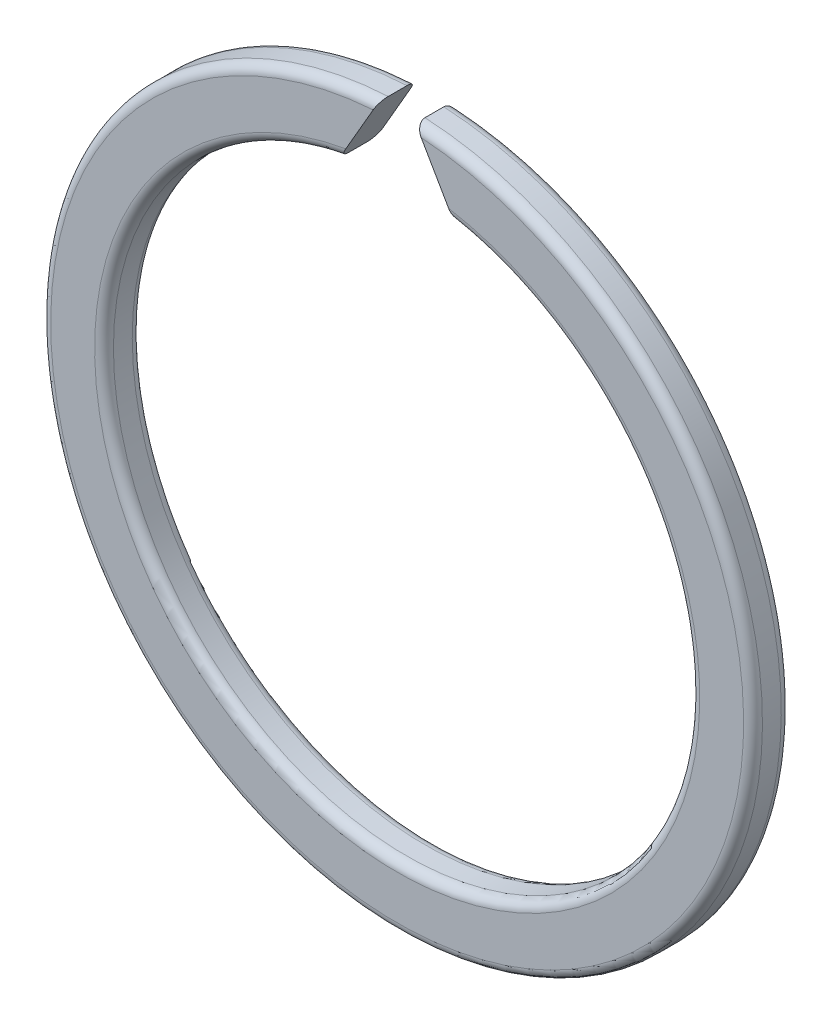
SolidWorks part; units mm, degrees
ref_plane "Front Plane" through (0, 0, 0) normal (0, 0, 1) x (1, 0, 0)
ref_plane "Top Plane" through (0, 0, 0) normal (0, 1, 0) x (1, 0, 0)
ref_plane "Right Plane" through (0, 0, 0) normal (1, 0, 0) x (0, 0, -1)
sketch "BodySke" plane through (0, 0, 0) normal (0, 0, 1) x (1, 0, 0)
  circle A0 centre (0, 0) radius 9.35
  circle A1 centre (0, 0) radius 11.35
extrude "BaseBody" add sketch "BodySke" along normal blind 1.2
sketch "SlitSke" plane through (0, 0, 0) normal (0, 0, 1) x (1, 0, 0)
  line L0 (0, 0) -> (0, 17.3673) construction
  line L1 (0, 12.35) -> (-1.8373, 9.1677)
  line L2 (-1.8373, 9.1677) -> (1.8373, 9.1677)
  line L3 (0, 12.35) -> (1.8373, 9.1677)
  circle A0 centre (0, 0) radius 9.35 construction
  point P9 (0, 9.1677)
  dimension "D2" = 12.35
extrude "Slit" cut sketch "SlitSke" along normal through all
fillet "Fillet1" radius 0.3 4 edges at (0, -9.35, 0) (0, -11.35, 0) (0, -9.35, 1.2) (0, -11.35, 1.2)
equation "\"D2@SlitSke\" = \"Groove_Diameter@BodySke\" / 2 + \"Groove_Width@BodySke\" * 1.5"
